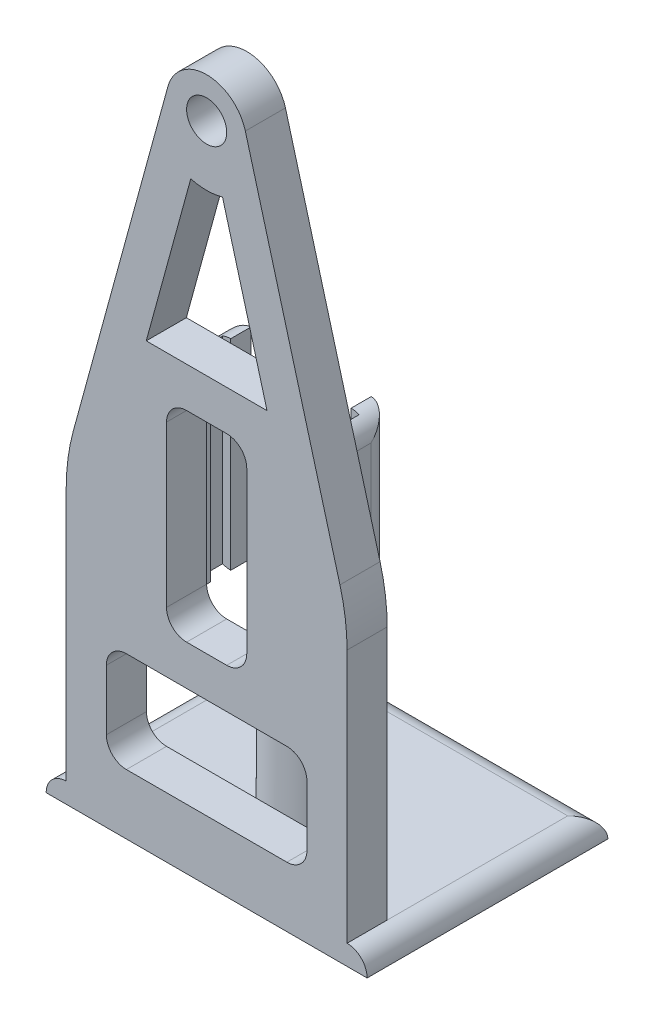
SolidWorks part; units mm, degrees
ref_plane "Front Plane" through (0, 0, 0) normal (0, 0, 1) x (1, 0, 0)
ref_plane "Top Plane" through (0, 0, 0) normal (0, 1, 0) x (1, 0, 0)
ref_plane "Right Plane" through (0, 0, 0) normal (1, 0, 0) x (0, 0, -1)
sketch "Sketch1" plane through (0, 0, 0) normal (0, 0, 1) x (1, 0, 0)
  line L0 (-40, 0) -> (40, 0)
  line L1 (40, 0) -> (40, 5)
  line L2 (40, 5) -> (-40, 5)
  line L3 (35, 5) -> (35, 75)
  line L4 (35, 75) -> (9.6453, 167.6398)
  line L5 (0, 0) -> (0, 175) construction
  line L6 (-35, 75) -> (-9.6453, 167.6398)
  line L7 (-35, 5) -> (-35, 75)
  line L8 (-40, 0) -> (-40, 5)
  circle A0 centre (0, 165) radius 10
  circle A1 centre (0, 165) radius 5
  point P4 (0, 165)
  point P12 (0, 5)
  dimension "D1" = 20
  dimension "D7" = 10
  dimension "D2" = 40
  dimension "D3" = 5
  dimension "D4" = 35
  dimension "D5" = 70
  dimension "D6" = 160
extrude "Boss-Extrude1" add sketch "Sketch1" along normal blind 10 contours L5 L0 L1 L2 | L2 L5 L6 L7 | L5 L2 L3 L4 | L0 L1 L2 L8 | A0 | A1 region at (20, 2.5, 0) region at (15.4023, 71.0999, 0) region at (-15.4023, 71.0999, 0)
sketch "Sketch2" plane through (0, 0, 0) normal (0, 0, -1) x (-1, 0, 0)
  line L1 (-40, 0) -> (40, 0)
  line L2 (-40, 0) -> (-40, 5)
  line L3 (-40, 5) -> (40, 5)
  line L4 (40, 0) -> (40, 5)
extrude "Boss-Extrude2" add sketch "Sketch2" along normal blind 50
sketch "Sketch3" plane through (0, 0, 0) normal (0, 0, -1) x (-1, 0, 0)
  line L1 (35, 5) -> (-35, 5) construction
  line L3 (0, 165) -> (0, 5) construction
  line L6 (-15, 100) -> (-20, 100)
  line L7 (15, 50) -> (20, 50)
  line L8 (15, 50) -> (15, 100)
  line L9 (15, 100) -> (20, 100)
  line L10 (20, 50) -> (20, 100)
  line L11 (-15, 50) -> (-15, 100)
  line L12 (-15, 50) -> (-20, 50)
  line L13 (-20, 50) -> (-20, 100)
  dimension "D3" = 5
  dimension "D4" = 50
  dimension "D6" = 15
extrude "Boss-Extrude3" add sketch "Sketch3" along normal blind 16
fillet "Fillet1" radius 50 2 edges at (-35, 75, 5) (35, 75, 5)
fillet "Fillet3" radius 5 3 edges at (0, 5, -50) (-40, 5, -20) (40, 5, -20)
fillet "Fillet7" radius 5 3 edges at (20, 75, -16) (20, 50, -8) (20, 100, -8)
fillet "Fillet8" radius 5 3 edges at (-20, 50, -8) (-20, 75, -16) (-20, 100, -8)
sketch "Sketch8" plane through (-15, 0, 0) normal (1, 0, 0) x (0, 0, -1)
  line L0 (16, 100) -> (0, 100) construction
  line L1 (11, 100) -> (6, 100)
  line L2 (11, 100) -> (11, 50)
  line L3 (11, 50) -> (6, 50)
  line L4 (6, 100) -> (6, 50)
  line L5 (16, 50) -> (0, 50) construction
  line L6 (16, 100) -> (16, 50) construction
  dimension "D1" = 5
  dimension "D2" = 5
extrude "Cut-Extrude4" cut sketch "Sketch8" against normal blind 2 and the other way blind 32
sketch "Sketch11" plane through (0, 5, 0) normal (0, 1, 0) x (1, 0, 0)
  line L0 (-35, 0) -> (35, 0) construction
  line L1 (35, 0) -> (35, 45) construction
  circle A0 centre (0, 16.5) radius 10
  dimension "D1" = 16.5
  dimension "D2" = 20
  dimension "D3" = 35
extrude "Boss-Extrude5" add sketch "Sketch11" along normal blind 18.75
sketch "Sketch14" plane through (0, 0, 0) normal (0, 0, -1) x (-1, 0, 0)
  line L10 (-15.053, 110) -> (15.053, 110)
  line L11 (-20, 40) -> (20, 40)
  line L12 (15, 100) -> (15, 50) construction
  line L13 (-5, 100) -> (5, 100)
  line L14 (-10, 95) -> (-10, 55)
  line L15 (25, 15) -> (25, 68.2813)
  line L16 (23.5811, 78.8406) -> (0, 165)
  line L17 (0, 165) -> (-23.5811, 78.8406)
  line L18 (-25, 68.2813) -> (-25, 15)
  line L19 (-25, 15) -> (25, 15)
  line L20 (25, 20) -> (25, 35)
  line L21 (15.053, 110) -> (3.9597, 150.5321)
  line L22 (-3.9597, 150.5321) -> (-15.053, 110)
  line L23 (-25, 35) -> (-25, 20)
  line L24 (-20, 15) -> (20, 15)
  line L25 (-5, 50) -> (5, 50)
  line L26 (10, 95) -> (10, 55)
  line L27 (-15, 50) -> (-15, 100) construction
  arc A7 (-25, 35) -> (-20, 40) centre (-20, 35) cw
  circle A8 centre (0, 165) radius 15
  arc A9 (25, 68.2813) -> (23.5811, 78.8406) centre (-15, 68.2813) ccw
  arc A10 (-23.5811, 78.8406) -> (-25, 68.2813) centre (15, 68.2813) ccw
  arc A13 (-3.9597, 150.5321) -> (3.9597, 150.5321) centre (0, 165) ccw
  arc A14 (20, 40) -> (25, 35) centre (20, 35) cw
  arc A15 (25, 20) -> (20, 15) centre (20, 20) cw
  arc A16 (-25, 20) -> (-20, 15) centre (-20, 20) ccw
  arc A17 (5, 50) -> (10, 55) centre (5, 55) ccw
  arc A18 (-10, 55) -> (-5, 50) centre (-5, 55) ccw
  arc A19 (5, 100) -> (10, 95) centre (5, 95) cw
  arc A20 (-5, 100) -> (-10, 95) centre (-5, 95) ccw
  dimension "D5" = 5
  dimension "D10" = 5
  dimension "D3" = 10
  dimension "D4" = 10
  dimension "D6" = 10
  dimension "D7" = 10
  dimension "D8" = 5
  dimension "D9" = 5
  dimension "D1" = 10
  dimension "D2" = 10
extrude "Cut-Extrude9" cut sketch "Sketch14" against normal blind 45 contours L23 A16 L24 A15 L20 A14 L11 A7 | A13 L22 L10 L21 | L14 A18 L25 A17 L26 A19 L13 A20 | L21 A13 L22 L10 | L20 A14 L11 A7 L23 A16 L24 A15 region at (0, 126.2364, 0) region at (0, 27.5, 0)
